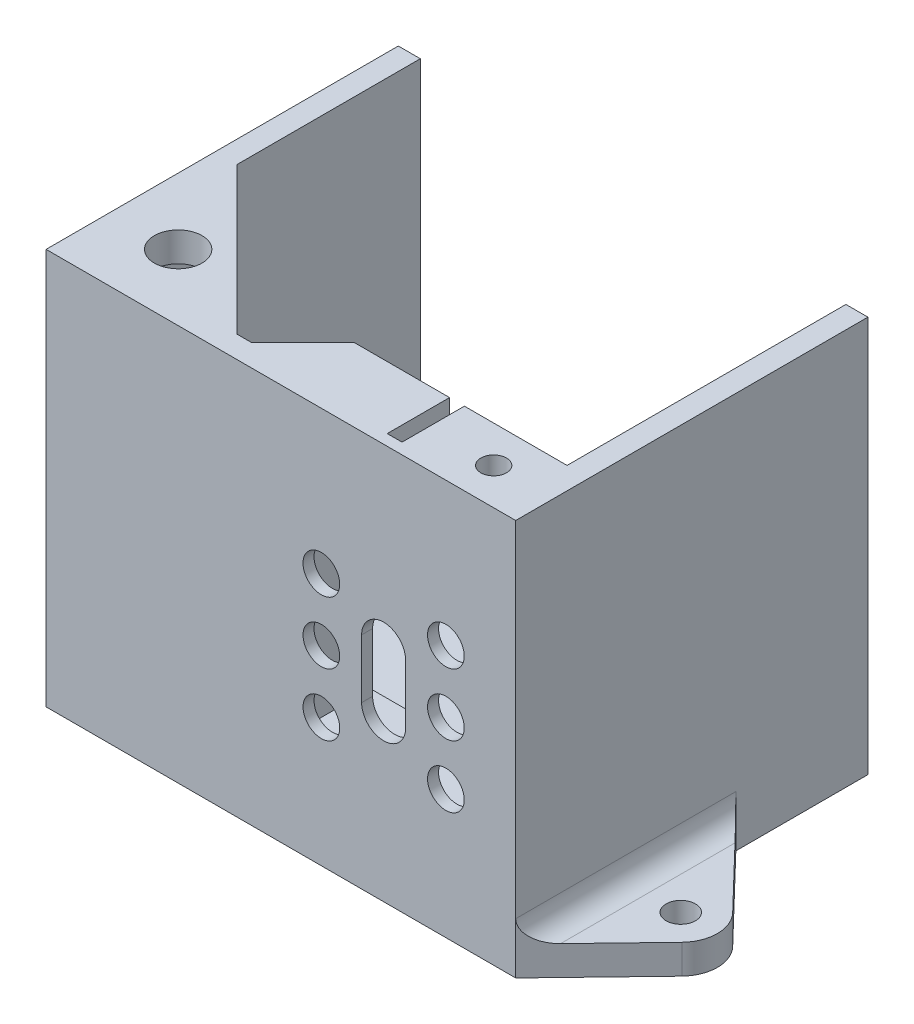
SolidWorks part; units mm, degrees
ref_plane "Płaszczyzna przednia" through (0, 0, 0) normal (0, 0, 1) x (1, 0, 0)
ref_plane "Płaszczyzna górna" through (0, 0, 0) normal (0, 1, 0) x (1, 0, 0)
ref_plane "Płaszczyzna prawa" through (0, 0, 0) normal (1, 0, 0) x (0, 0, -1)
sketch "Sketch1" plane through (0, 0, 0) normal (0, 1, 0) x (1, 0, 0)
  line L1 (-32, 24) -> (32, 24)
  line L2 (-32, 24) -> (-32, -24)
  line L3 (-32, -24) -> (32, -24)
  line L4 (32, 24) -> (32, -24)
  line L5 (-32, 24) -> (32, -24) construction
  line L6 (-32, -24) -> (32, 24) construction
  point P0 (0, 0)
  dimension "D1" = 64
  dimension "D2" = 48
extrude "Boss-Extrude1" add sketch "Sketch1" along normal blind 4
sketch "Sketch2" plane through (0, 0, 0) normal (0, -1, 0) x (1, 0, 0)
  line L9 (-20.6514, -16) -> (-22.3257, -13.1)
  line L10 (-22.3257, -13.1) -> (-25.6743, -13.1)
  line L11 (-25.6743, -13.1) -> (-27.3486, -16)
  line L12 (-27.3486, -16) -> (-25.6743, -18.9)
  line L13 (-25.6743, -18.9) -> (-22.3257, -18.9)
  line L14 (-22.3257, -18.9) -> (-20.6514, -16)
  line L15 (-32, -24) -> (-32, 24) construction
  line L16 (32, -24) -> (-32, -24) construction
  circle A0 centre (-24, -16) radius 2.9 construction
  dimension "D3" = 5.8
  dimension "D1" = 8
  dimension "D2" = 8
extrude "Cut-Extrude1" cut sketch "Sketch2" against normal blind 2.4
sketch "Sketch4" plane through (0, 0, 0) normal (0, -1, 0) x (1, 0, 0)
  line L0 (-32, -24) -> (-32, 24) construction
  line L1 (9.3486, 10) -> (7.6743, 12.9)
  line L2 (7.6743, 12.9) -> (4.3257, 12.9)
  line L3 (4.3257, 12.9) -> (2.6514, 10)
  line L4 (2.6514, 10) -> (4.3257, 7.1)
  line L5 (4.3257, 7.1) -> (7.6743, 7.1)
  line L6 (7.6743, 7.1) -> (9.3486, 10)
  line L8 (32, -24) -> (-32, -24) construction
  circle A0 centre (6, 10) radius 2.9 construction
  dimension "D3" = 5.8
  dimension "D1" = 38
  dimension "D2" = 34
extrude "Cut-Extrude2" cut sketch "Sketch4" against normal blind 2.4
sketch "Sketch6" plane through (0, 4, 0) normal (0, 1, 0) x (1, 0, 0)
  line L0 (-29, 21) -> (-29, 24)
  line L1 (-32, 24) -> (32, 24)
  line L2 (-32, 24) -> (-32, -24)
  line L3 (-32, -24) -> (32, -24)
  line L4 (32, 24) -> (32, -24)
  line L5 (-29, 21) -> (29, 21)
  line L6 (-29, 21) -> (-29, -21)
  line L7 (-29, -21) -> (29, -21)
  line L8 (29, 21) -> (29, -21)
  line L9 (-29, 21) -> (29, -21) construction
  line L10 (-29, -21) -> (29, 21) construction
  line L11 (29, 21) -> (29, 24)
  point P6 (0, 0)
  line M1 (32, -24) -> (32, 24)
  line M2 (32, 24) -> (-32, 24)
  line M3 (-32, 24) -> (-32, -24)
  line M4 (-32, -24) -> (32, -24)
  dimension "D1" = 58
  dimension "D2" = 42
extrude "Boss-Extrude3" add sketch "Sketch6" along normal blind 50 contours L11 L8 L7 L6 L0 M2 M3 M4 M1 region at (-29.8, 4, 0)
sketch "Sketch9" plane through (0, 4, 0) normal (0, 1, 0) x (1, 0, 0)
  line L0 (1, -13) -> (-7, -21)
  line L3 (29, -13) -> (1, -13)
  line L5 (-29, -21) -> (29, -21) construction
  line L6 (-7, -21) -> (29, -21)
  line L7 (1, -13) -> (-7, -21)
  line L9 (29, -21) -> (29, -13)
  line M3 (29, -21) -> (29, 24)
  line M6 (-29, -21) -> (29, -21)
  dimension "D1" = 8
  dimension "D2" = 8
  dimension "D3" = 28
extrude "Boss-Extrude4" add sketch "Sketch9" along normal blind 50 contours L3 L0 M3 M6 region at (12.9167, 4, 17.1667)
sketch "Sketch10" plane through (0, 0, 13) normal (0, 0, -1) x (-1, 0, 0)
  line L0 (-29, 54) -> (-29, 4) construction
  line L1 (-26.75, 38.75) -> (-1.25, 38.75)
  line L2 (-26.75, 38.75) -> (-26.75, 13.25)
  line L3 (-26.75, 13.25) -> (-1.25, 13.25)
  line L4 (-1.25, 38.75) -> (-1.25, 13.25)
  line L5 (-26.75, 38.75) -> (-1.25, 13.25) construction
  line L6 (-26.75, 13.25) -> (-1.25, 38.75) construction
  line L7 (-14, 38.75) -> (-14, 54) construction
  line L9 (-29, 54) -> (-1, 54) construction
  line L15 (-15.0119, 38.75) -> (-12.9881, 38.75)
  line L16 (-15.0119, 38.75) -> (-15.0119, 54)
  line L17 (-15.0119, 54) -> (-12.9881, 54)
  line L18 (-12.9881, 38.75) -> (-12.9881, 54)
  line L19 (-15.0119, 38.75) -> (-12.9881, 54) construction
  line L20 (-15.0119, 54) -> (-12.9881, 38.75) construction
  point P0 (-14, 26)
  point P9 (-14, 46.375)
  line M5 (-1, 54) -> (-29, 54)
  dimension "D1" = 25.5
  dimension "D2" = 25.5
  dimension "D3" = 15
  dimension "D5" = 28
extrude "Cut-Extrude4" cut sketch "Sketch10" against normal blind 9.5 contours L1 L18 L16 M5 | L4 L1 L2 L3 region at (14, 26, 13) region at (14, 46.375, 13)
sketch "Sketch13" plane through (0, 54, 0) normal (0, 1, 0) x (1, 0, 0)
  line L1 (29, -13) -> (-7.9463, -13)
  line L2 (29, -13) -> (29, -14)
  line L3 (29, -14) -> (-7.9463, -14)
  line L4 (-7.9463, -13) -> (-7.9463, -14)
  dimension "D1" = 1
extrude "Cut-Extrude6" cut sketch "Sketch13" against normal blind 32
sketch "Sketch15" plane through (0, 54, 0) normal (0, 1, 0) x (1, 0, 0)
  line L0 (-29, -1) -> (-9, -21)
  line L5 (-29, 24) -> (-29, -21) construction
  line L6 (-29, -21) -> (-7, -21) construction
  line L7 (-29, 24) -> (-29, -21) construction
  line L8 (-29, -1) -> (-29, -21)
  line L9 (-29, -21) -> (-9, -21)
  line L10 (-32, 24) -> (-32, -24) construction
  line L11 (-32, -24) -> (32, -24) construction
  circle A0 centre (-23, -15) radius 3.25
  dimension "D3" = 9
  dimension "D5" = 6.5
  dimension "D1" = 20
  dimension "D2" = 20
  dimension "D4" = 9
extrude "Boss-Extrude5" add sketch "Sketch15" against normal blind 4
sketch "Sketch17" plane through (0, 54, 0) normal (0, 1, 0) x (1, 0, 0)
  line L0 (32, -24) -> (32, 24) construction
  line L7 (-32, -24) -> (32, -24) construction
  line L8 (24, -19) -> (24, -24) construction
  line L9 (24, -19) -> (32, -19) construction
  line L11 (24, -15.6514) -> (21.1, -17.3257)
  line L12 (21.1, -17.3257) -> (21.1, -20.6743)
  line L13 (21.1, -20.6743) -> (24, -22.3486)
  line L14 (24, -22.3486) -> (26.9, -20.6743)
  line L15 (26.9, -20.6743) -> (26.9, -17.3257)
  line L16 (26.9, -17.3257) -> (24, -15.6514)
  circle A0 centre (24, -19) radius 2.9 construction
  dimension "D1" = 8
  dimension "D3" = 5.8
  dimension "D2" = 5
extrude "Cut-Extrude7" cut sketch "Sketch17" against normal blind 7
sketch "Sketch18" plane through (0, 0, 14) normal (0, 0, -1) x (-1, 0, 0)
  line L0 (-15.0119, 54) -> (-29, 54) construction
  line L1 (-26.9, 49.6) -> (-21.1, 49.6)
  line L2 (-26.9, 49.6) -> (-26.9, 47)
  line L3 (-26.9, 47) -> (-21.1, 47)
  line L4 (-21.1, 49.6) -> (-21.1, 47)
  line L5 (-32, 54) -> (-32, 0) construction
  point P6 (-24, 49.6)
  dimension "D1" = 7
  dimension "D2" = 2.6
  dimension "D3" = 5.8
  dimension "D4" = 8
extrude "Cut-Extrude8" cut sketch "Sketch18" against normal blind 5
sketch "Sketch19" plane through (0, 54, 0) normal (0, 1, 0) x (1, 0, 0)
  line L0 (25.75, -19) -> (22.25, -19) construction
  line L6 (22.25, -19) -> (24, -17.25) construction
  line L8 (24, -17.25) -> (24, -20.75) construction
  line L10 (20.7023, -15.4012) -> (27.2977, -15.4012)
  line L11 (20.7023, -15.4012) -> (20.7023, -22.5988)
  line L12 (20.7023, -22.5988) -> (27.2977, -22.5988)
  line L13 (27.2977, -15.4012) -> (27.2977, -22.5988)
  line L14 (20.7023, -22.5988) -> (27.2977, -22.5988)
  line L15 (20.7023, -22.5988) -> (20.7023, -15.4012)
  line L16 (20.7023, -15.4012) -> (27.2977, -15.4012)
  line L17 (27.2977, -22.5988) -> (27.2977, -15.4012)
  line L18 (20.7023, -22.5988) -> (27.2977, -15.4012) construction
  line L19 (20.7023, -15.4012) -> (27.2977, -22.5988) construction
  circle A0 centre (24, -19) radius 1.75
  line M1 (24, -15.6514) -> (26.9, -17.3257)
  line M2 (26.9, -17.3257) -> (26.9, -20.6743)
  line M3 (26.9, -20.6743) -> (24, -22.3486)
  line M4 (24, -22.3486) -> (21.1, -20.6743)
  line M5 (21.1, -20.6743) -> (21.1, -17.3257)
  line M6 (21.1, -17.3257) -> (24, -15.6514)
  dimension "D1" = 3.5
extrude "Boss-Extrude8" add sketch "Sketch19" against normal blind 4.4 contours A0 M1 M6 M5 M4 M3 M2 region at (25.4057, 54, 16.5653)
fillet "Fillet1" radius 1.5 2 edges at (-29, 50, 11) (-19, 50, 21)
sketch "Sketch20" plane through (0, 0, 0) normal (0, -1, 0) x (1, 0, 0)
  line L0 (32, 24) -> (43.1021, 12.4677)
  line L1 (39.5, 9) -> (32, 9) construction
  line L2 (32, -6) -> (43.1021, 5.5323)
  line L3 (-32, -24) -> (-42.9789, -14.5912)
  line L4 (32, -6) -> (32, 24)
  line L6 (-32, 2) -> (-32, -24)
  line L8 (-39.5, -11) -> (-32, -11) construction
  line L9 (-32, 2) -> (-42.9789, -7.4088)
  line L10 (-20.8246, -16) -> (-22.4123, -13.25) construction
  line L11 (-22.4123, -18.75) -> (-20.8246, -16) construction
  line L12 (-25.5877, -18.75) -> (-22.4123, -18.75) construction
  line L13 (-27.1754, -16) -> (-25.5877, -18.75) construction
  line L14 (-25.5877, -13.25) -> (-27.1754, -16) construction
  line L15 (-22.4123, -13.25) -> (-25.5877, -13.25) construction
  line L16 (9.1754, 10) -> (7.5877, 12.75) construction
  line L17 (7.5877, 7.25) -> (9.1754, 10) construction
  line L18 (4.4123, 7.25) -> (7.5877, 7.25) construction
  line L19 (2.8246, 10) -> (4.4123, 7.25) construction
  line L20 (4.4123, 12.75) -> (2.8246, 10) construction
  line L21 (7.5877, 12.75) -> (4.4123, 12.75) construction
  line L22 (-22.3257, -13.1) -> (-25.6743, -13.1) construction
  line L23 (-20.6514, -16) -> (-22.3257, -13.1) construction
  line L24 (-22.3257, -13.1) -> (-25.6743, -13.1) construction
  line L25 (-20.6514, -16) -> (-22.3257, -13.1) construction
  line L26 (32, -24) -> (32, 24)
  line L27 (32, 24) -> (-32, 24)
  line L28 (-32, 24) -> (-32, -24)
  line L29 (-32, -24) -> (32, -24)
  line L30 (32, -6) -> (32, 24)
  line L32 (-32, 2) -> (-32, -24)
  line L36 (9.3486, 10) -> (7.6743, 12.9)
  line L37 (7.6743, 7.1) -> (9.3486, 10)
  line L38 (4.3257, 7.1) -> (7.6743, 7.1)
  line L39 (2.6514, 10) -> (4.3257, 7.1)
  line L40 (4.3257, 12.9) -> (2.6514, 10)
  line L41 (7.6743, 12.9) -> (4.3257, 12.9)
  line L42 (9.3486, 10) -> (7.6743, 12.9) construction
  line L43 (7.6743, 7.1) -> (9.3486, 10) construction
  line L44 (4.3257, 7.1) -> (7.6743, 7.1) construction
  line L45 (2.6514, 10) -> (4.3257, 7.1) construction
  line L46 (4.3257, 12.9) -> (2.6514, 10) construction
  line L47 (7.6743, 12.9) -> (4.3257, 12.9) construction
  line L48 (-20.6514, -16) -> (-22.3257, -13.1)
  line L49 (-22.3257, -18.9) -> (-20.6514, -16)
  line L50 (-25.6743, -18.9) -> (-22.3257, -18.9)
  line L51 (-27.3486, -16) -> (-25.6743, -18.9)
  line L52 (-25.6743, -13.1) -> (-27.3486, -16)
  line L53 (-22.3257, -13.1) -> (-25.6743, -13.1)
  line L54 (-20.6514, -16) -> (-22.3257, -13.1) construction
  line L55 (-22.3257, -18.9) -> (-20.6514, -16) construction
  line L56 (-25.6743, -18.9) -> (-22.3257, -18.9) construction
  line L57 (-27.3486, -16) -> (-25.6743, -18.9) construction
  line L58 (-25.6743, -13.1) -> (-27.3486, -16) construction
  line L59 (-22.3257, -13.1) -> (-25.6743, -13.1) construction
  circle A0 centre (39.5, 9) radius 2
  circle A1 centre (-39.5, -11) radius 2
  arc A2 (43.1021, 5.5323) -> (43.1021, 12.4677) centre (39.5, 9) ccw
  arc A3 (-42.5162, -7.0122) -> (-42.5162, -14.9878) centre (-39.5, -11) ccw
  dimension "D1" = 0
  dimension "D2" = 0
  dimension "D3" = 0
extrude "Boss-Extrude9" add sketch "Sketch20" against normal blind 4 contours L9 A3 L3 L23 A1 | L2 A2 L0 L4 A0 region at (36.4432, 0, 9) region at (-36.5396, 0, -11)
fillet "Fillet2" radius 3 2 edges at (-32, 4, -11) (32, 4, 9)
sketch "Sketch22" plane through (0, 2.4, 0) normal (0, -1, 0) x (1, 0, 0)
  line L0 (4.3257, 12.9) -> (7.6743, 7.1) construction
  line L1 (7.6743, 7.1) -> (7.6743, 12.9) construction
  line L2 (7.6743, 12.9) -> (4.3257, 7.1) construction
  line L3 (-25.6743, -18.9) -> (-22.3257, -13.1) construction
  line L4 (-22.3257, -13.1) -> (-22.3257, -18.9) construction
  line L5 (-25.6743, -13.1) -> (-22.3257, -18.9) construction
  circle A0 centre (-24, -16) radius 1.75
  circle A1 centre (6, 10) radius 1.75
  dimension "D1" = 3.5
  dimension "D2" = 3.5
extrude "Cut-Extrude9" cut sketch "Sketch22" against normal blind 2
sketch "Sketch23" plane through (0, 0, 22.5) normal (0, 0, -1) x (-1, 0, 0)
  line L0 (-14, 13.25) -> (-14, 38.6846) construction
  line L1 (-26.75, 13.25) -> (-1.25, 13.25) construction
  line L2 (-14, 26) -> (-14, 22) construction
  line L3 (-14, 26) -> (-14, 30) construction
  line L4 (-14, 30) -> (-14, 22) construction
  line L5 (-11, 30) -> (-11, 22)
  line L6 (-17, 30) -> (-17, 22)
  line L7 (-14, 38.6846) -> (-14, 54) construction
  line L9 (-12.9881, 54) -> (-15.0119, 54) construction
  line L10 (-22.4853, 17.5147) -> (-5.5147, 17.5147) construction
  line L11 (-22.4853, 34.4853) -> (-22.4853, 17.5147) construction
  line L12 (-5.5147, 34.4853) -> (-5.5147, 17.5147) construction
  line L13 (-14, 26) -> (-1.25, 26) construction
  line L14 (-1.25, 38.75) -> (-1.25, 13.25) construction
  line L15 (-1.25, 26) -> (-26.75, 26) construction
  line L16 (-26.75, 38.75) -> (-26.75, 13.25) construction
  line L17 (-22.4853, 17.5147) -> (-22.4853, 34.4853) construction
  line L18 (-22.4853, 34.4853) -> (-5.5147, 34.4853) construction
  line L19 (-5.5147, 17.5147) -> (-5.5147, 34.4853) construction
  line L20 (-22.4853, 17.5147) -> (-5.5147, 34.4853) construction
  line L21 (-22.4853, 34.4853) -> (-5.5147, 17.5147) construction
  circle A1 centre (-22.4853, 34.4853) radius 2.5
  circle A2 centre (-5.5147, 34.4853) radius 2.5
  circle A3 centre (-5.5147, 17.5147) radius 2.5
  circle A4 centre (-22.4853, 17.5147) radius 2.5
  arc A6 (-11, 30) -> (-17, 30) centre (-14, 30) ccw
  arc A7 (-17, 22) -> (-11, 22) centre (-14, 22) ccw
  circle A8 centre (-22.4853, 26) radius 2.5
  circle A9 centre (-5.5147, 26) radius 2.5
  point P2 (0, 0)
  point P3 (0, 0)
  point P19 (-14, 26)
  point P37 (-14, 26)
  dimension "D5" = 5
  dimension "D6" = 5
  dimension "D7" = 12
  dimension "D8" = 12
  dimension "D2" = 5
  dimension "D3" = 5
  dimension "D1" = 5
  dimension "D4" = 5
extrude "Cut-Extrude10" cut sketch "Sketch23" against normal blind 3
